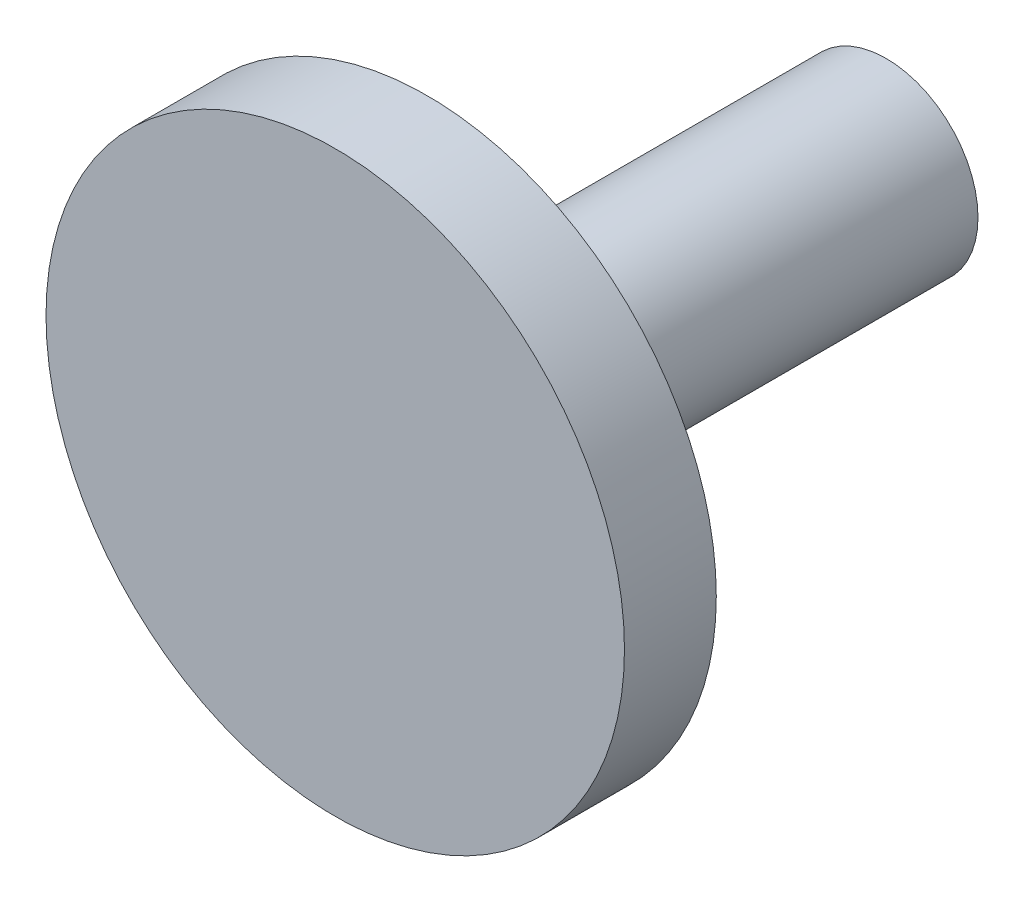
SolidWorks part; units mm, degrees
ref_plane "Front Plane" through (0, 0, 0) normal (0, 0, 1) x (1, 0, 0)
ref_plane "Top Plane" through (0, 0, 0) normal (0, 1, 0) x (1, 0, 0)
ref_plane "Right Plane" through (0, 0, 0) normal (1, 0, 0) x (0, 0, -1)
sketch "Sketch1" plane through (0, 0, 0) normal (0, 0, 1) x (1, 0, 0)
  circle A0 centre (0, 0) radius 15.75
  circle A1 centre (0, 0) radius 5
extrude "Boss-Extrude1" add sketch "Sketch1" along normal blind 5 contours A0
extrude "Boss-Extrude2" add sketch "Sketch1<3>" against normal blind 25 contours A1
sketch "Sketch1<3>" plane through (0, 0, 0) normal (0, 0, 1) x (1, 0, 0) same geometry as "Sketch1"
